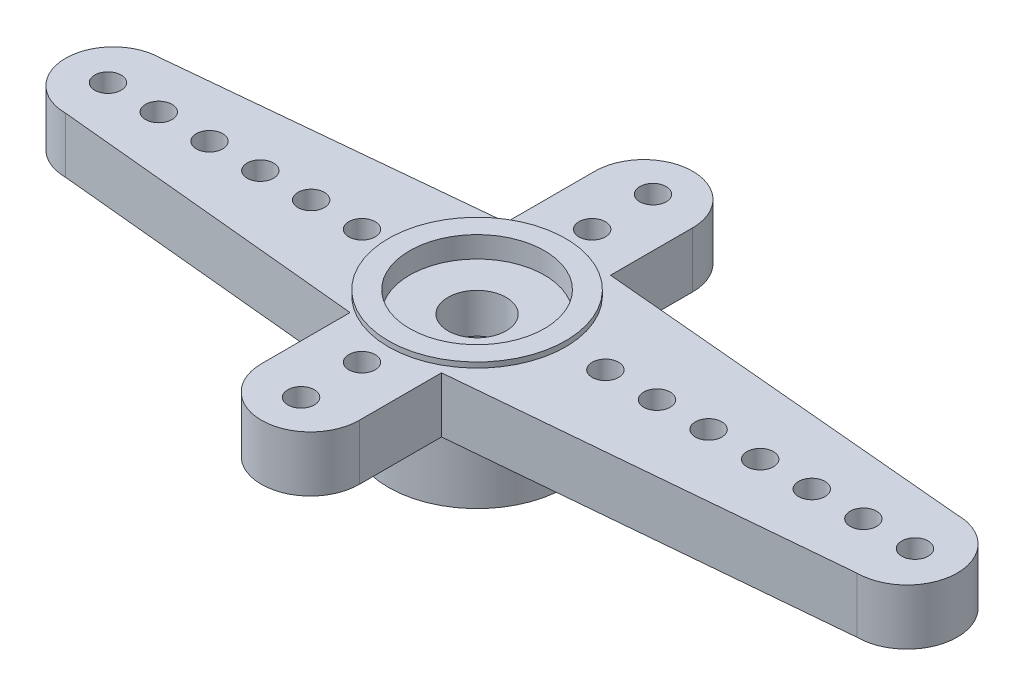
SolidWorks part; units mm, degrees
ref_plane "Plan de face" through (0, 0, 0) normal (0, 0, 1) x (1, 0, 0)
ref_plane "Plan de dessus" through (0, 0, 0) normal (0, 1, 0) x (1, 0, 0)
ref_plane "Plan de droite" through (0, 0, 0) normal (1, 0, 0) x (0, 0, -1)
sketch "Esquisse1" plane through (0, 0, 0) normal (0, 1, 0) x (1, 0, 0)
  line L0 (-7.2643, 3.3473) -> (8.85, 1.9)
  line L1 (-7.2643, -3.3473) -> (8.85, -1.9)
  line L2 (-10.75, 0) -> (10.75, 0) construction
  line L3 (-7.4, 0) -> (-7.4, -3.35) construction
  line L6 (-9.25, -6.3) -> (-5.55, -6.3)
  line L7 (-9.25, 0) -> (-5.55, 0)
  line L8 (-9.25, -6.3) -> (-9.25, 6.3)
  line L9 (-9.25, 6.3) -> (-5.55, 6.3)
  line L10 (-5.55, -6.3) -> (-5.55, 6.3)
  line L11 (-9.25, 2.95) -> (-9.25, -2.95) construction
  line L12 (-9.25, 2.95) -> (-21.15, 1.8)
  line L13 (-21.15, -1.8) -> (-9.25, -2.95)
  arc A0 (-7.2643, 3.3473) -> (-7.5357, 3.3473) centre (-7.4, 0) ccw
  arc A1 (8.85, -1.9) -> (8.85, 1.9) centre (8.85, 0) ccw
  circle A2 centre (-7.4, 0) radius 1.1
  arc A3 (-7.5357, 3.3473) -> (-7.2643, 3.3473) centre (-7.4, 0) cw
  arc A5 (-7.5357, -3.3473) -> (-7.2643, -3.3473) centre (-7.4, 0) ccw
  arc A6 (-7.2643, -3.3473) -> (-7.5357, -3.3473) centre (-7.4, 0) cw
  circle A7 centre (-7.4, 6.3) radius 1.85
  circle A8 centre (-7.4, -6.3) radius 1.85
  circle A9 centre (-21.15, 0) radius 1.8
  point P2 (-7.4, 3.35)
  point P3 (8.85, 1.9)
  point P8 (-10.75, 0)
  point P9 (10.75, 0)
  point P12 (0, 0)
  point P18 (-22.95, 0)
  point P27 (-7.4, 0)
  point P34 (-7.4, 8.15)
  point P35 (-7.4, -8.15)
  point P36 (-9.25, 0)
  dimension "D1" = 6.7
  dimension "D3" = 3.8
  dimension "D4" = 2.2
  dimension "D7" = 16.3
  dimension "D2" = 3.6
  dimension "D5" = 33.7
  dimension "D6" = 3.7
  dimension "D8" = 21.5
  dimension "D9" = 5.132
  dimension "D10" = 5.9
extrude "Boss.-Extru.1" add sketch "Esquisse1" along normal blind 2.1 contours A0 L2 A2 A1 L0 | L2 A0 L1 A1 A2 | L8 | A5 L1 L10 L7 A2 L8 | L8 A8 L10 L1 A5 | A8 L6 | A8 L6 | L9 A7 | L9 A7 | A7 L8 A0 L0 L10 | A9 region at (1.6589, 0, -1.2652) region at (-7.4, 0, -2.6751) region at (-7.4, 0, 2.6751) region at (1.6589, 0, 1.2652) region at (-7.4, 0, -5.5148) region at (-7.4, 0, -7.0852) region at (-7.4, 0, 7.0852) region at (-7.4, 0, 5.5148) region at (-14.1592, 0, 0)
sketch "Esquisse2" plane through (0, 2.1, 0) normal (0, 1, 0) x (1, 0, 0)
  circle A1 centre (-7.4, 0) radius 1.1 construction
  circle A4 centre (-7.4, 0) radius 3.35
  circle A5 centre (-7.4, 0) radius 2.55
  circle A6 centre (-7.4, 0) radius 1.1
  dimension "D1" = 6.7
  dimension "D2" = 0.8
extrude "Boss.-Extru.2" add sketch "Esquisse2" along normal blind 0.2 contours A4 A5 region at (-10.6552, 2.1, 0)
sketch "Esquisse9" plane through (0, 2.3, 0) normal (0, 1, 0) x (1, 0, 0)
  circle A0 centre (-7.4, 0) radius 2.55 construction
  circle A1 centre (-7.4, 0) radius 2.55
extrude "Enlèv. mat.-Extru.4" cut sketch "Esquisse9" against normal blind 0.8
sketch "Esquisse5" plane through (0, 0, 0) normal (0, -1, 0) x (1, 0, 0)
  circle A6 centre (-7.4, 0) radius 2.55 construction
  circle A15 centre (-7.4, 0) radius 2.55
  circle A16 centre (-7.4, 0) radius 3.35
  dimension "D1" = 6.7
extrude "Boss.-Extru.3" add sketch "Esquisse5" along normal blind 4.8 from surface starting at face at (-7.4, 2.3, 2.55)
sketch "Esquisse7" plane through (0, 2.1, 0) normal (0, 1, 0) x (1, 0, 0)
  line L0 (-7.4, 0) -> (10.75, 0) construction
  line L1 (-7.4, 0) -> (-7.4, -3.35) construction
  line L2 (9.15, 0) -> (10.75, 0) construction
  circle A25 centre (-7.4, 4.35) radius 0.5
  circle A26 centre (-7.4, 6.65) radius 0.5
  arc A31 (8.85, -1.9) -> (8.85, 1.9) centre (8.85, 0) ccw construction
  circle A32 centre (-2.55, 0) radius 0.5
  circle A46 centre (-7.4, 0) radius 3.35 construction
  circle A47 centre (-7.4, 0) radius 3.35
  circle A48 centre (-0.6, 0) radius 0.5
  circle A49 centre (1.35, 0) radius 0.5
  circle A50 centre (3.3, 0) radius 0.5
  circle A51 centre (5.25, 0) radius 0.5
  circle A52 centre (7.2, 0) radius 0.5
  circle A53 centre (9.15, 0) radius 0.5
  arc A61 (-5.55, 6.3) -> (-9.25, 6.3) centre (-7.4, 6.3) ccw construction
  circle A62 centre (-7.4, -6.65) radius 0.5
  circle A63 centre (-7.4, -4.35) radius 0.5
  circle A64 centre (-11.75, 0) radius 0.5
  circle A65 centre (-13.67, 0) radius 0.5
  circle A66 centre (-15.59, 0) radius 0.5
  circle A67 centre (-17.51, 0) radius 0.5
  circle A68 centre (-19.43, 0) radius 0.5
  circle A69 centre (-21.35, 0) radius 0.5
  arc A70 (-21.15, 1.8) -> (-21.15, -1.8) centre (-21.15, 0) ccw construction
  point P3 (9.15, 0)
  point P10 (-4.05, 0)
  point P11 (-7.4, 3.35)
  point P38 (-10.75, 0)
  point P39 (-22.95, 0)
  point P43 (-7.4, 8.15)
  point P52 (-7.4, -8.15)
  dimension "D1" = 1.6
  dimension "D3" = 1
  dimension "D2" = 1
  dimension "D5" = 1.5
  dimension "D4" = 1
  dimension "D6" = 1.5
  dimension "D8" = 1.6
  dimension "D9" = 6
  dimension "D7" = 7
extrude "Enlèv. mat.-Extru.3" cut sketch "Esquisse7" against normal up to next contours A32 | A26 | A25 | A48 | A49 | A50 | A51 | A52 | A53 | A63 | A62 | A69 | A68 | A67 | A66 | A65 | A64
